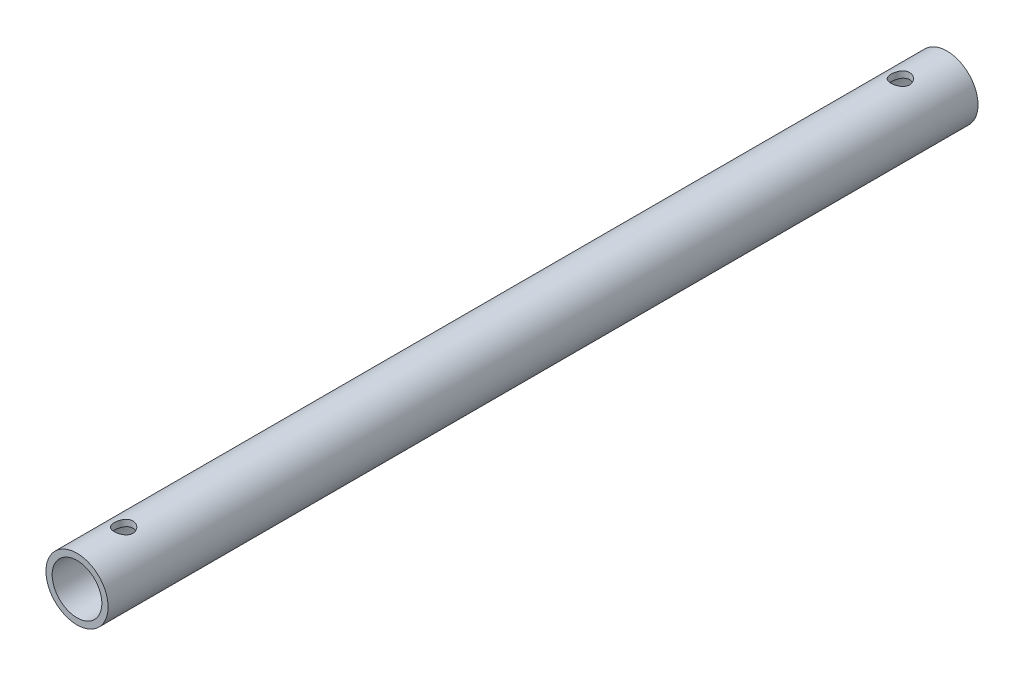
SolidWorks part; units mm, degrees
ref_plane "Ön Düzlem" through (0, 0, 0) normal (0, 0, 1) x (1, 0, 0)
ref_plane "Üst Düzlem" through (0, 0, 0) normal (0, 1, 0) x (1, 0, 0)
ref_plane "Sağ Düzlem" through (0, 0, 0) normal (1, 0, 0) x (0, 0, -1)
sketch "Sketch1" plane through (0, 0, 0) normal (0, 0, 1) x (1, 0, 0)
  circle A0 centre (0, 0) radius 5
  circle A1 centre (0, 0) radius 4
  dimension "D1" = 10
  dimension "D2" = 1
extrude "Boss-Extrude1" add sketch "Sketch1" along normal blind 140
sketch "Sketch3" plane through (0, 0, 0) normal (0, 1, 0) x (1, 0, 0)
  line L0 (5, 0) -> (-5, 0) construction
  circle A0 centre (0, -7.5) radius 1.5
  dimension "D1" = 3
  dimension "D2" = 7.5
extrude "Cut-Extrude1" cut sketch "Sketch3" against normal blind 175 and the other way blind 175
sketch "Sketch4" plane through (0, 0, 0) normal (0, 1, 0) x (1, 0, 0)
  line L0 (-5, -140) -> (5, -140) construction
  circle A0 centre (0, -132.5) radius 1.5
  dimension "D1" = 3
  dimension "D2" = 7.5
extrude "Cut-Extrude2" cut sketch "Sketch4" against normal blind 10 and the other way blind 10
